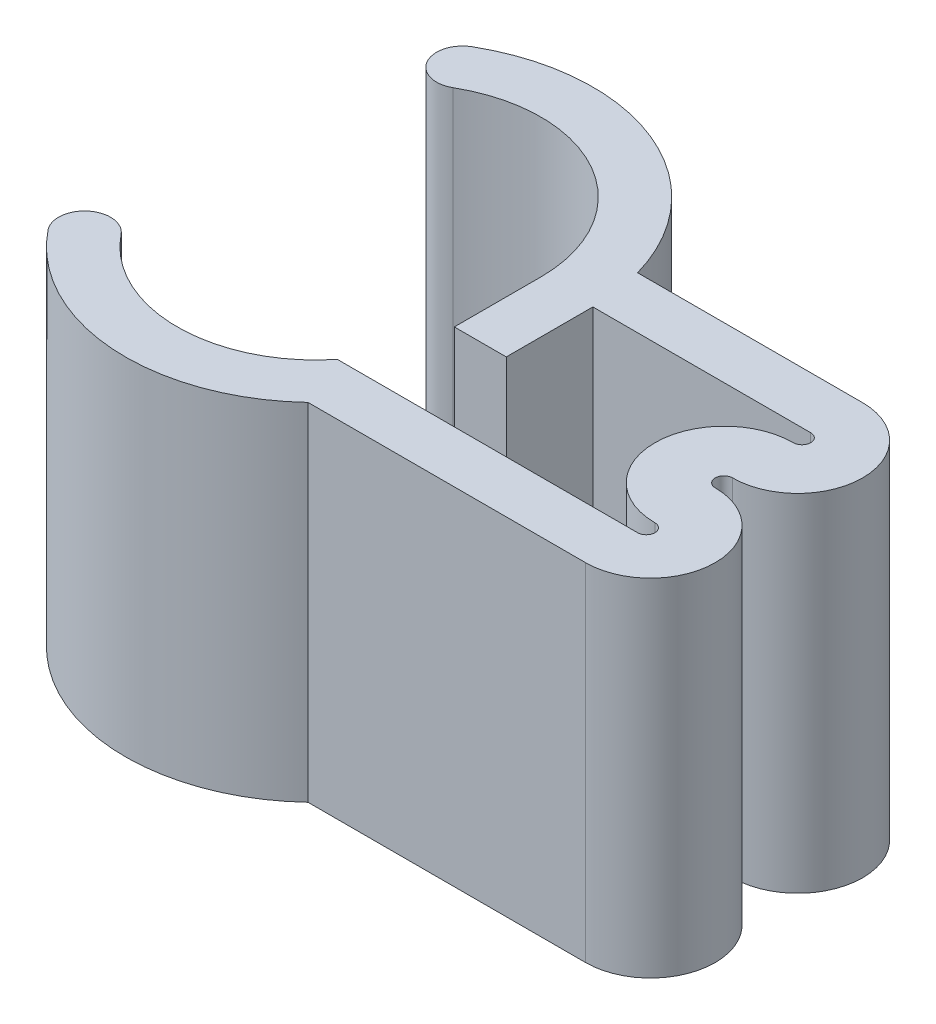
SolidWorks part; units mm, degrees
ref_plane "Front Plane" through (0, 0, 0) normal (0, 0, 1) x (1, 0, 0)
ref_plane "Top Plane" through (0, 0, 0) normal (0, 1, 0) x (1, 0, 0)
ref_plane "Right Plane" through (0, 0, 0) normal (1, 0, 0) x (0, 0, -1)
sketch "Sketch1" plane through (0, 0, 0) normal (0, 1, 0) x (1, 0, 0)
  line L0 (3, 0) -> (15.583, 0)
  line L1 (2.583, 3) -> (15.583, 3)
  line L2 (-8, 0) -> (-8, -5) construction
  line L3 (15.583, 0) -> (15.583, -10) construction
  line L4 (15.583, -10) -> (-17.1257, -10) construction
  line L5 (15.583, -10) -> (-1.755, -10)
  line L6 (-0.4502, -13) -> (15.583, -13)
  line L9 (0, 0) -> (0, -5)
  line L10 (0, -5) -> (3, -5)
  line L11 (3, 0) -> (3, -5)
  arc A0 (0, 0) -> (-12, 6.9282) centre (-8, 0) ccw
  arc A1 (-12, 6.9282) -> (-13.5, 9.5263) centre (-12.75, 8.2272) cw
  arc A2 (-13.5, 9.5263) -> (2.583, 3) centre (-8, 0) cw
  arc A3 (-1.755, -10) -> (-14.245, -10) centre (-8, -5) cw
  arc A4 (-14.245, -10) -> (-16.5869, -11.875) centre (-15.4159, -10.9375) ccw
  arc A5 (-16.5869, -11.875) -> (-0.4502, -13) centre (-8, -5) ccw
  arc A6 (15.583, -10) -> (15.583, -9) centre (15.583, -9.5) ccw
  arc A7 (15.583, -9) -> (15.583, -1) centre (15.583, -5) cw
  arc A8 (15.583, -1) -> (15.583, 0) centre (15.583, -0.5) ccw
  arc A9 (15.583, 3) -> (15.583, -4.5163) centre (15.583, -0.7581) cw
  arc A10 (15.583, -4.5163) -> (15.583, -5.5163) centre (15.583, -5.0163) ccw
  arc A11 (15.583, -5.5163) -> (15.583, -13) centre (15.583, -9.2581) cw
  dimension "D2" = 1.5
  dimension "D7" = 1.5
  dimension "D9" = 0.5
  dimension "D10" = 0.5
  dimension "D11" = 0.5
  dimension "D12" = 11
  dimension "D3" = 13
  dimension "D5" = 5
  dimension "D6" = 10
  dimension "D8" = 3
  dimension "D13" = 8
  dimension "D14" = 3
  dimension "D15" = 5
extrude "Boss-Extrude1" add sketch "Sketch1" along normal blind 20
